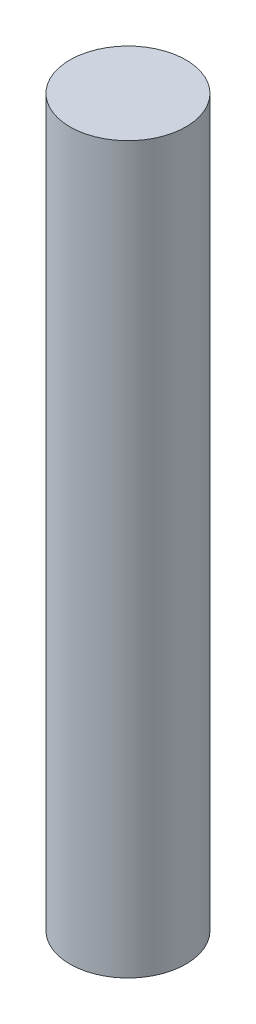
SolidWorks part; units mm, degrees
ref_plane "Front Plane" through (0, 0, 0) normal (0, 0, 1) x (1, 0, 0)
ref_plane "Top Plane" through (0, 0, 0) normal (0, 1, 0) x (1, 0, 0)
ref_plane "Right Plane" through (0, 0, 0) normal (1, 0, 0) x (0, 0, -1)
sketch "Sketch1" plane through (0, 0, 0) normal (0, 1, 0) x (1, 0, 0)
  circle A0 centre (-31.8716, 9.5412) radius 8
  dimension "D1" = 16
extrude "Boss-Extrude1" add sketch "Sketch1" along normal blind 100
